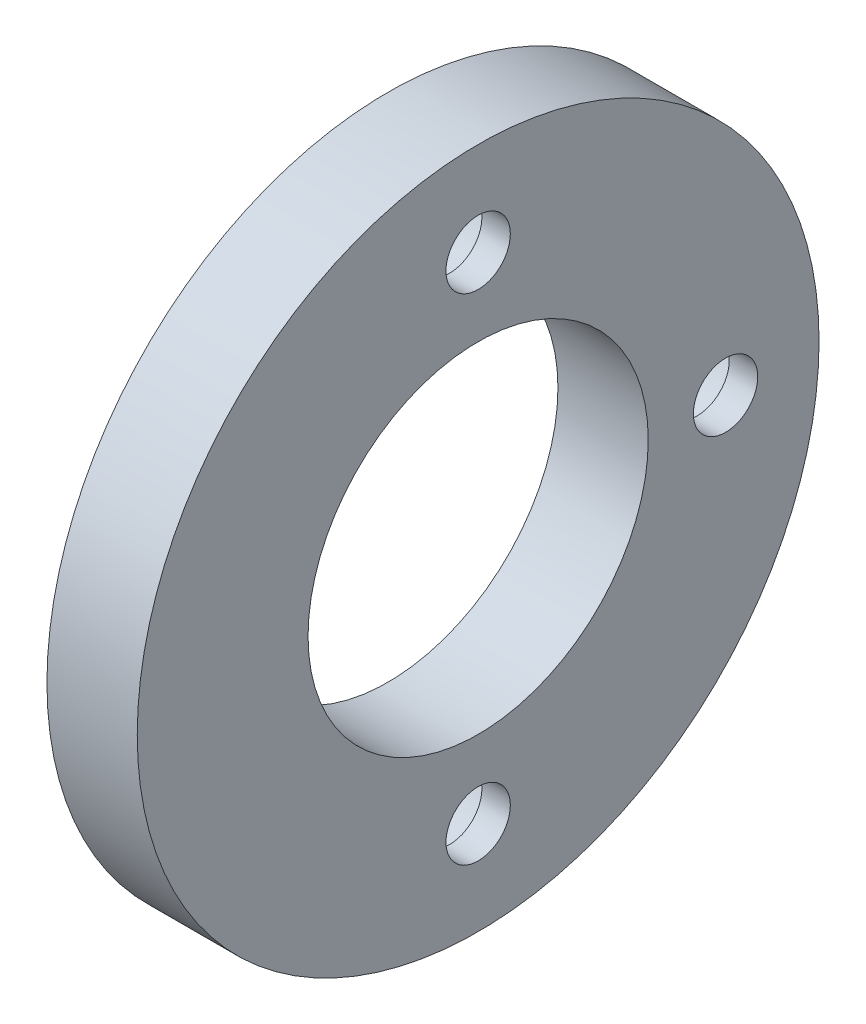
SolidWorks part; units mm, degrees
ref_plane "Front Plane" through (0, 0, 0) normal (0, 0, 1) x (1, 0, 0)
ref_plane "Top Plane" through (0, 0, 0) normal (0, 1, 0) x (1, 0, 0)
ref_plane "Right Plane" through (0, 0, 0) normal (1, 0, 0) x (0, 0, -1)
sketch "Sketch1" plane through (0, 0, 0) normal (1, 0, 0) x (0, 0, -1)
  circle A0 centre (0, 0) radius 17.4625
  circle A1 centre (0, 0) radius 35
  circle A2 centre (0, 25.4) radius 3.302
  circle A3 centre (25.4, 0) radius 3.302
  circle A4 centre (0, -25.4) radius 3.302
  circle A5 centre (-25.4, 0) radius 3.302 [skipped]
  dimension "D1" = 70
  dimension "D3" = 6.604
  dimension "D5" = 34.925
  dimension "D2" = 25.4
  dimension "D4" = 4
extrude "Boss-Extrude1" add sketch "Sketch1" along normal blind 9.271
sketch "Sketch2" plane through (0, 0, 0) normal (-1, 0, 0) x (0, 0, 1)
  circle A0 centre (0, 25.4) radius 6.35
  circle A1 centre (25.4, 0) radius 6.35 [skipped]
  circle A2 centre (0, -25.4) radius 6.35
  circle A3 centre (-25.4, 0) radius 6.35
  dimension "D1" = 12.7
  dimension "D2" = 4
extrude "Cut-Extrude1" cut sketch "Sketch2" against normal blind 6.35
